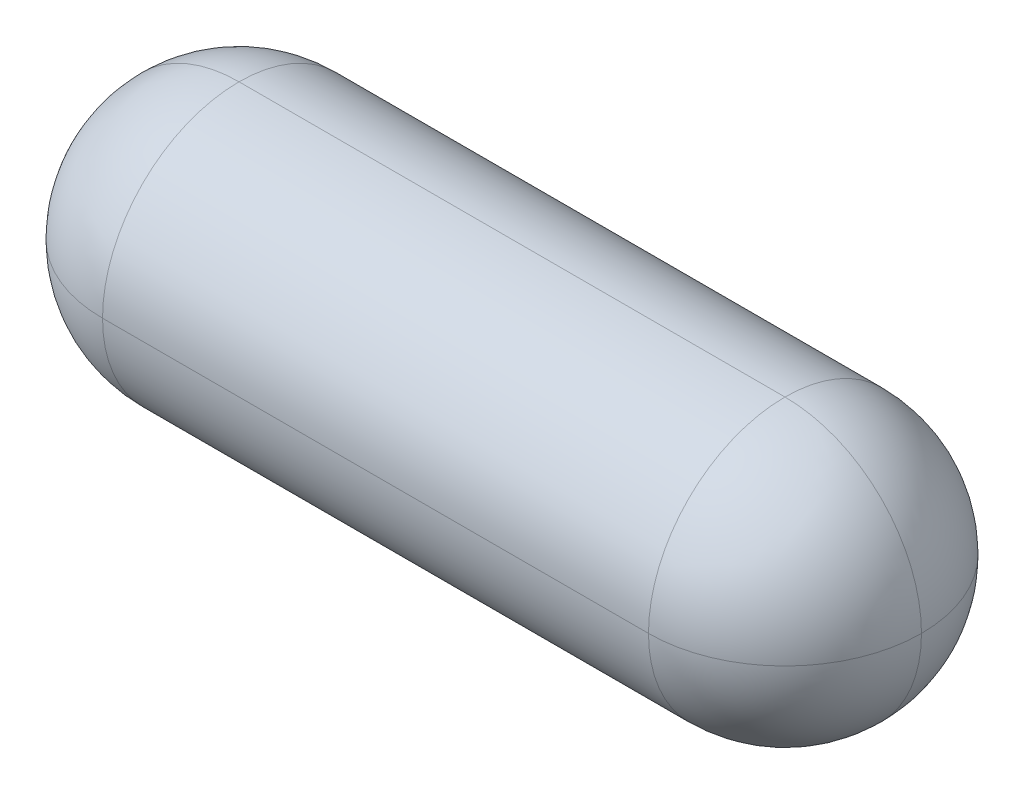
SolidWorks part; units mm, degrees
ref_plane "Płaszczyzna przednia" through (0, 0, 0) normal (0, 0, 1) x (1, 0, 0)
ref_plane "Płaszczyzna górna" through (0, 0, 0) normal (0, 1, 0) x (1, 0, 0)
ref_plane "Płaszczyzna prawa" through (0, 0, 0) normal (1, 0, 0) x (0, 0, -1)
sketch "Sketch1" plane through (0, 0, 0) normal (0, 0, 1) x (1, 0, 0)
  line L0 (-0.9772, 0.4752) -> (-0.9772, -5.5248)
  line L1 (-0.9772, -5.5248) -> (17.0228, -5.5248)
  line L2 (17.0228, -5.5248) -> (17.0228, 0.4752)
  line L3 (17.0228, 0.4752) -> (-0.9772, 0.4752)
  dimension "D1" = 18
  dimension "D2" = 6
extrude "Boss-Extrude1" add sketch "Sketch1" along normal blind 6
fillet "Fillet1" radius 3 4 edges at (8.0228, -5.5248, 6) (8.0228, -5.5248, 0) (8.0228, 0.4752, 0) (8.0228, 0.4752, 6)
fillet "Fillet2" radius 3 8 edges at (-0.9772, -0.4035, 0.8787) (-0.9772, -0.4035, 5.1213) (-0.9772, -4.6461, 5.1213) (-0.9772, -4.6461, 0.8787) (17.0228, -0.4035, 0.8787) (17.0228, -4.6461, 0.8787) (17.0228, -4.6461, 5.1213) (17.0228, -0.4035, 5.1213)
